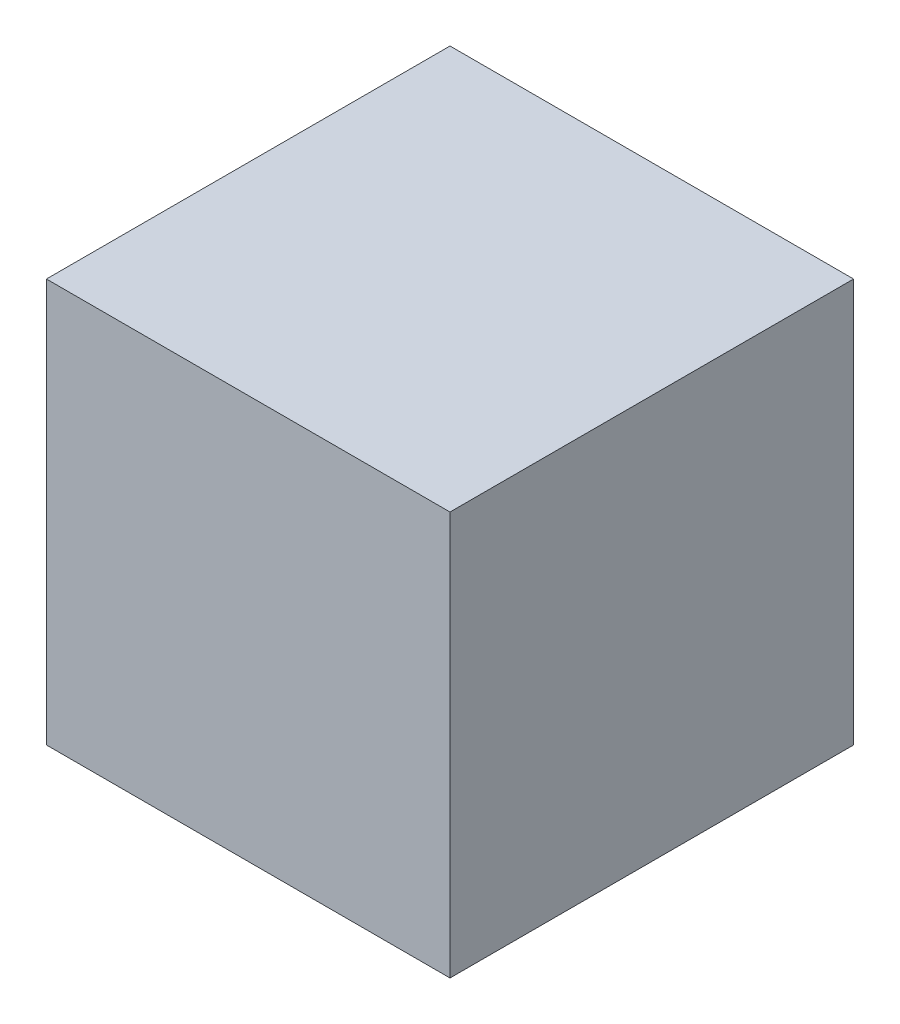
SolidWorks part; units mm, degrees
ref_plane "Front Plane" through (0, 0, 0) normal (0, 0, 1) x (1, 0, 0)
ref_plane "Top Plane" through (0, 0, 0) normal (0, 1, 0) x (1, 0, 0)
ref_plane "Right Plane" through (0, 0, 0) normal (1, 0, 0) x (0, 0, -1)
sketch "Sketch1" plane through (0, 0, 0) normal (0, 1, 0) x (1, 0, 0)
  line L1 (0, 0) -> (150, 0)
  line L2 (0, 0) -> (0, 150)
  line L3 (0, 150) -> (150, 150)
  line L4 (150, 0) -> (150, 150)
extrude "Boss-Extrude1" add sketch "Sketch1" along normal blind 150
sketch "Sketch2" plane through (0, 0, 0) normal (0, 0, 1) x (1, 0, 0)
  line L0 (0, 150) -> (150, 0) construction
  line L1 (0, 0) -> (150, 150) construction
  point P4 (75, 75)
sketch "Sketch3" plane through (0, 0, -150) normal (0, 0, -1) x (-1, 0, 0)
  line L0 (-150, 150) -> (0, 0) construction
  line L1 (-150, 150) -> (-150, 0) construction
  line L2 (0, 150) -> (-150, 0) construction
  point P9 (-75, 75)
ref_plane "Plane1" through (0, 75, 0) normal (0, 1, 0) x (1, 0, 0)
sketch "Sketch4" plane through (0, 75, 0) normal (0, 1, 0) x (1, 0, 0)
  line L0 (75, 150) -> (75, 0) construction
ref_plane "Plane2" through (75, 0, 0) normal (1, 0, 0) x (0, 0, -1)
ref_axis "Axis2" through (75, 75, -235.2712) along (0, 0, 1)
